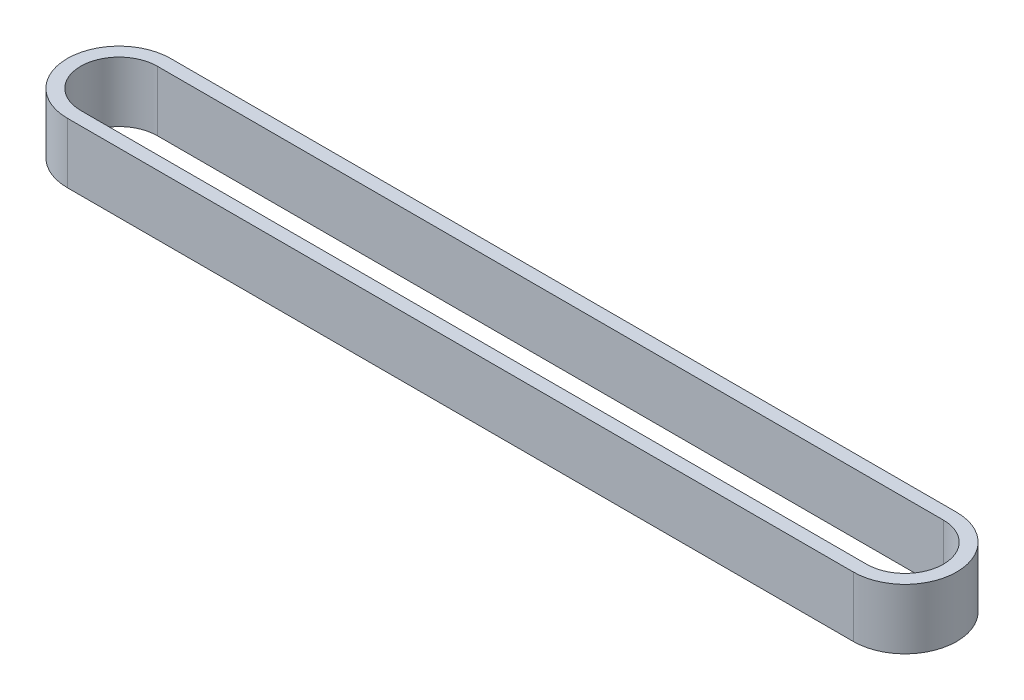
SolidWorks part; units mm, degrees
material "Rubber"
ref_plane "Front Plane" through (0, 0, 0) normal (0, 0, 1) x (1, 0, 0)
ref_plane "Top Plane" through (0, 0, 0) normal (0, 1, 0) x (1, 0, 0)
ref_plane "Right Plane" through (0, 0, 0) normal (1, 0, 0) x (0, 0, -1)
sketch "Sketch1" plane through (0, 0, 0) normal (0, 1, 0) x (1, 0, 0)
  line L0 (-58.7502, 0) -> (58.7502, 0) construction
  line L1 (-58.7502, 0) -> (58.7502, 0) construction
  line L2 (-58.7502, 7.7296) -> (58.7502, 7.7296)
  line L3 (-58.7502, -7.7296) -> (58.7502, -7.7296)
  line L4 (-58.7502, 5.7296) -> (58.7502, 5.7296)
  line L5 (-58.7502, -5.7296) -> (58.7502, -5.7296)
  circle A0 centre (-58.7502, 0) radius 5.7296 construction
  circle A1 centre (58.7502, 0) radius 5.7296 construction
  arc A2 (-58.7502, 7.7296) -> (-58.7502, -7.7296) centre (-58.7502, 0) ccw
  arc A3 (58.7502, -7.7296) -> (58.7502, 7.7296) centre (58.7502, 0) ccw
  arc A4 (58.7502, -5.7296) -> (58.7502, 5.7296) centre (58.7502, 0) ccw
  arc A5 (-58.7502, 5.7296) -> (-58.7502, -5.7296) centre (-58.7502, 0) ccw
  point P4 (0, 0)
  point P7 (0, 0)
  dimension "D1" = 11.4592
  dimension "D2" = 2
  dimension "D3" = 117.5004
  dimension "D4" = 2
extrude "Boss-Extrude1" add sketch "Sketch1" along normal mid plane 9
equation "\"t\"= 12'teeth"
equation "\"p\"= 3'pitch(mm)"
equation "\"pd\"= \"t\" * \"p\" / pi'pitch diam in mm"
equation "\"D1@Sketch1\"=\"pd\""
